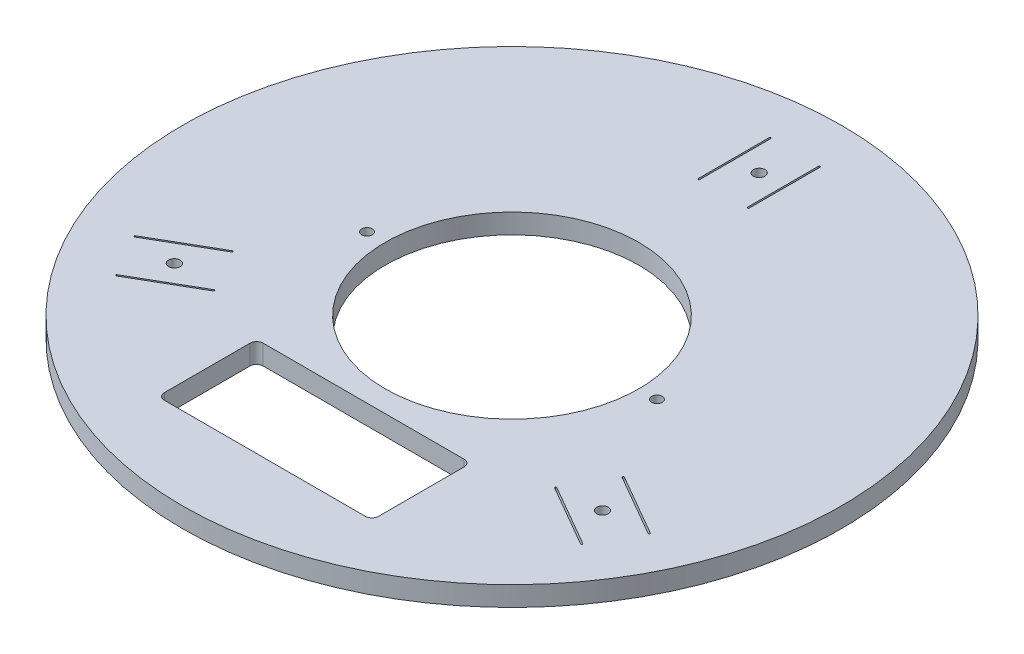
SolidWorks part; units mm, degrees
ref_plane "Front Plane" through (0, 0, 0) normal (0, 0, 1) x (1, 0, 0)
ref_plane "Top Plane" through (0, 0, 0) normal (0, 1, 0) x (1, 0, 0)
ref_plane "Right Plane" through (0, 0, 0) normal (1, 0, 0) x (0, 0, -1)
sketch "Sketch2" plane through (0, 0, 0) normal (0, 1, 0) x (1, 0, 0)
  circle A0 centre (0, 0) radius 100
  dimension "D1" = 200
extrude "Boss-Extrude1" add sketch "Sketch2" along normal blind 6
sketch "Sketch3" plane through (0, 6, 0) normal (0, 1, 0) x (1, 0, 0)
  line L0 (0, 0) -> (0, 100) construction
  line L1 (-7.5, 75) -> (7.5, 75) construction
  line L3 (-7.75, 64) -> (-7.25, 64)
  line L4 (-7.75, 64) -> (-7.75, 86)
  line L5 (-7.75, 86) -> (-7.25, 86)
  line L6 (-7.25, 64) -> (-7.25, 86)
  line L7 (-7.75, 64) -> (-7.25, 86) construction
  line L8 (-7.75, 86) -> (-7.25, 64) construction
  line L9 (7.25, 64) -> (7.75, 64)
  line L10 (7.25, 64) -> (7.25, 86)
  line L11 (7.25, 86) -> (7.75, 86)
  line L12 (7.75, 64) -> (7.75, 86)
  line L13 (7.25, 64) -> (7.75, 86) construction
  line L14 (7.25, 86) -> (7.75, 64) construction
  line L30 (59.3006, -25.2883) -> (78.3532, -36.2883)
  line L31 (59.3006, -25.2883) -> (59.0506, -25.7213)
  line L32 (59.0506, -25.7213) -> (78.1032, -36.7213)
  line L33 (78.3532, -36.2883) -> (78.1032, -36.7213)
  line L34 (51.8006, -38.2787) -> (70.8532, -49.2787)
  line L35 (51.8006, -38.2787) -> (51.5506, -38.7117)
  line L36 (51.5506, -38.7117) -> (70.6032, -49.7117)
  line L37 (70.8532, -49.2787) -> (70.6032, -49.7117)
  line L38 (-51.5506, -38.7117) -> (-70.6032, -49.7117)
  line L39 (-51.5506, -38.7117) -> (-51.8006, -38.2787)
  line L40 (-51.8006, -38.2787) -> (-70.8532, -49.2787)
  line L41 (-70.6032, -49.7117) -> (-70.8532, -49.2787)
  line L42 (-59.0506, -25.7213) -> (-78.1032, -36.7213)
  line L43 (-59.0506, -25.7213) -> (-59.3006, -25.2883)
  line L44 (-59.3006, -25.2883) -> (-78.3532, -36.2883)
  line L45 (-78.1032, -36.7213) -> (-78.3532, -36.2883)
  circle A0 centre (0, 0) radius 100 construction
  circle A1 centre (0, 75) radius 1.75
  circle A2 centre (64.9519, -37.5) radius 1.75
  circle A3 centre (-64.9519, -37.5) radius 1.75
  point P8 (0, 75)
  point P36 (0, 0)
  point P37 (0, 0)
  point P44 (0, 0)
  dimension "D6" = 3.5
  dimension "D1" = 15
  dimension "D2" = 22
  dimension "D3" = 0.5
  dimension "D4" = 75
  dimension "D5" = 3
  dimension "D7" = 3
extrude "Cut-Extrude1" cut sketch "Sketch3" against normal through all
sketch "Sketch4" plane through (0, 6, 0) normal (0, 1, 0) x (1, 0, 0)
  circle A0 centre (0, 0) radius 38.5
  dimension "D1" = 77
extrude "Cut-Extrude2" cut sketch "Sketch4" against normal through all
sketch "Sketch5" plane through (0, 6, 0) normal (0, 1, 0) x (1, 0, 0)
  line L0 (0, 0) -> (50000, 0) construction
  line L1 (0, 0) -> (0, 50000) construction
  circle A0 centre (-44, 0) radius 1.6
  circle A1 centre (44, 0) radius 1.6
  dimension "D2" = 3.2
  dimension "D1" = 44
extrude "Cut-Extrude3" cut sketch "Sketch5" against normal through all
sketch "Sketch6" plane through (0, 6, 0) normal (0, 1, 0) x (1, 0, 0)
  line L1 (-32.5, -45) -> (32.5, -45)
  line L2 (-32.5, -45) -> (-32.5, -75)
  line L3 (-32.5, -75) -> (32.5, -75)
  line L4 (32.5, -45) -> (32.5, -75)
  point P4 (0, -45)
  dimension "D1" = 45
  dimension "D2" = 30
  dimension "D3" = 65
extrude "Cut-Extrude4" cut sketch "Sketch6" against normal through all
fillet "Fillet1" radius 2 4 edges at (32.5, 3, 45) (32.5, 3, 75) (-32.5, 3, 75) (-32.5, 3, 45)
fillet "Fillet2" radius 0.2 24 edges at (-7.75, 3, -64) (-7.75, 3, -86) (-7.25, 3, -86) (-7.25, 3, -64) (-51.5506, 3, 38.7117) (-70.6032, 3, 49.7117) (-70.8532, 3, 49.2787) (-59.3006, 3, 25.2883) (-59.0506, 3, 25.7213) (-78.1032, 3, 36.7213) (-78.3532, 3, 36.2883) (51.5506, 3, 38.7117) (51.8006, 3, 38.2787) (70.8532, 3, 49.2787) (70.6032, 3, 49.7117) (59.0506, 3, 25.7213) (59.3006, 3, 25.2883) (78.3532, 3, 36.2883) (78.1032, 3, 36.7213) (7.25, 3, -64) (7.25, 3, -86) (7.75, 3, -86) (7.75, 3, -64) (-51.8006, 3, 38.2787)
equation "\"Leg_Spacing\"=15"
equation "\"D1@Sketch3\"=\"Leg_Spacing\""
equation "\"Leaf_Spring_Slot_Width\"=22"
equation "\"D2@Sketch3\"=\"Leaf_Spring_Slot_Width\""
equation "\"Leaf_Spring_Thickness\"=0.5"
equation "\"D3@Sketch3\"=\"Leaf_Spring_Thickness\""
equation "\"Inner_Radius\"=75"
equation "\"D4@Sketch3\"=\"Inner_Radius\""
equation "\"Camera\"=77"
equation "\"D1@Sketch4\"=\"Camera\""
